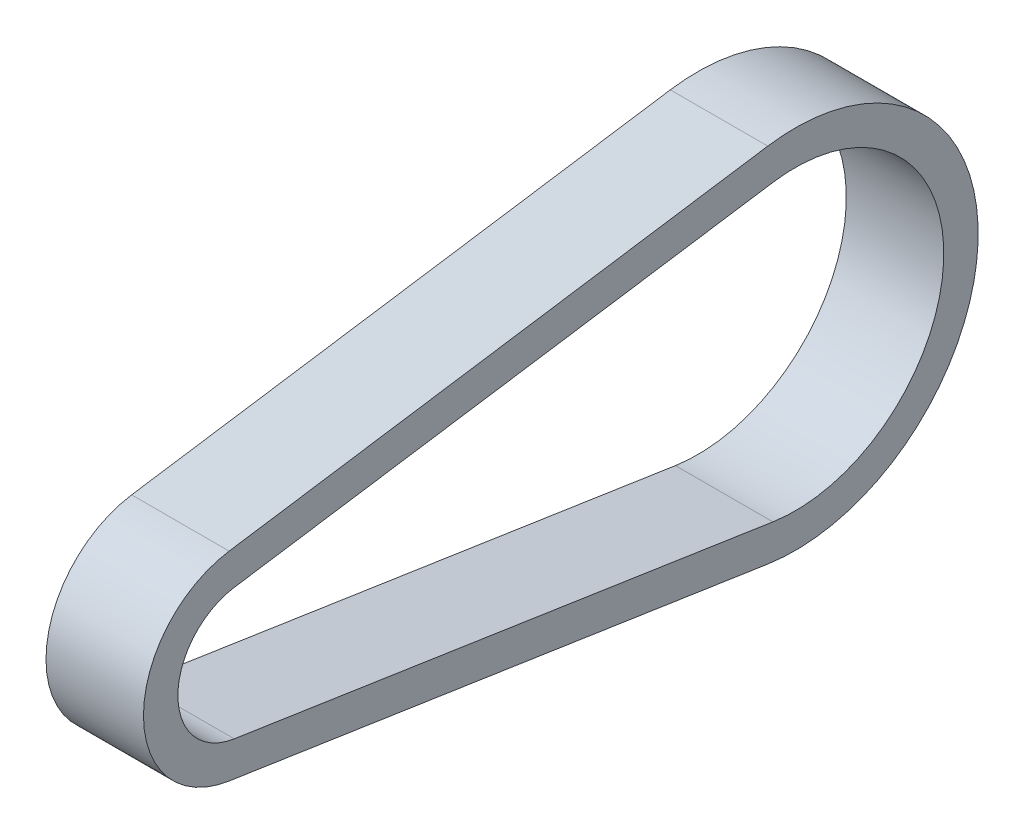
SolidWorks part; units mm, degrees
ref_plane "Front Plane" through (0, 0, 0) normal (0, 0, 1) x (1, 0, 0)
ref_plane "Top Plane" through (0, 0, 0) normal (0, 1, 0) x (1, 0, 0)
ref_plane "Right Plane" through (0, 0, 0) normal (1, 0, 0) x (0, 0, -1)
other "Bounding Box"
ref_plane "Default Plane" through (-8.9266, -12.7485, 0) normal (-0.1736, 0.9848, 0) x (0.9848, 0.1736, 0)
sketch "Sketch1" plane through (0, 0, 0) normal (1, 0, 0) x (0, 0, -1)
  line L0 (0, 0) -> (50.8762, 0) construction
  line L1 (-0.9154, 6.0551) -> (48.8241, 13.5745)
  line L2 (-0.9154, -6.0551) -> (48.8241, -13.5745)
  line L3 (-1.39, 9.1945) -> (48.3495, 16.7138)
  line L4 (-1.39, -9.1945) -> (48.3495, -16.7138)
  line L5 (-6.1239, 0) -> (-9.2989, 0) construction
  line L6 (64.6049, 0) -> (67.7799, 0) construction
  arc A0 (-0.9154, 6.0551) -> (-0.9154, -6.0551) centre (0, 0) ccw
  arc A1 (48.8241, -13.5745) -> (48.8241, 13.5745) centre (50.8762, 0) ccw
  arc A2 (-1.39, 9.1945) -> (-1.39, -9.1945) centre (0, 0) ccw
  arc A3 (48.3495, -16.7138) -> (48.3495, 16.7138) centre (50.8762, 0) ccw
  dimension "D2" = 3.175
  dimension "D4" = 12.2479
  dimension "D5" = 27.4574
  dimension "D1" = 50.8762
extrude "Boss-Extrude1" add sketch "Sketch1" along normal mid plane 9
